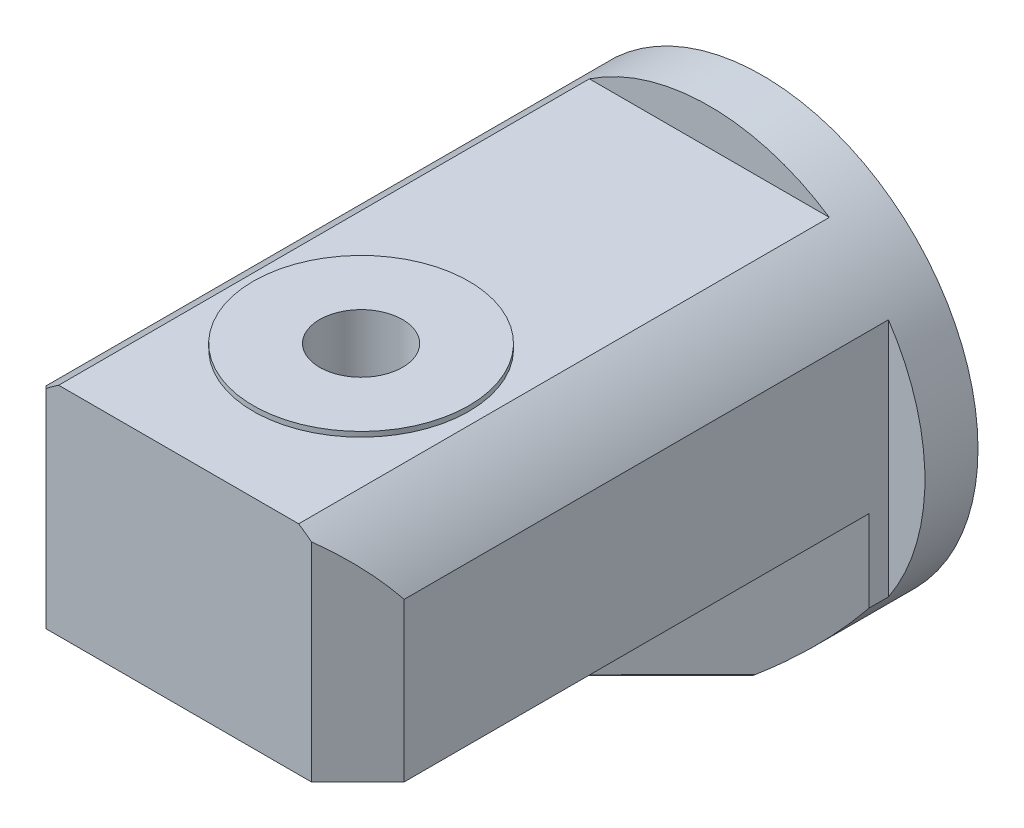
SolidWorks part; units mm, degrees
material "Cast Stainless Steel"
ref_plane "Front Plane" through (0, 0, 0) normal (0, 0, 1) x (1, 0, 0)
ref_plane "Top Plane" through (0, 0, 0) normal (0, 1, 0) x (1, 0, 0)
ref_plane "Right Plane" through (0, 0, 0) normal (1, 0, 0) x (0, 0, -1)
sketch "Sketch3" plane through (0, 0, 0) normal (0, 1, 0) x (1, 0, 0)
  circle A0 centre (0, 0) radius 130
extrude "Boss-Extrude1" add sketch "Sketch3" along normal blind 352
sketch "Sketch11" plane through (0, 352, 0) normal (0, 1, 0) x (1, 0, 0)
  line L0 (0, 0) -> (0, -108)
  line L1 (-72.3602, -108) -> (72.3602, -108)
  line L2 (0, 0) -> (-54.0967, 0)
  line L3 (-72.3602, 108) -> (72.3602, 108)
  line L4 (0, 0) -> (0, 40.1674)
  line L5 (0, 0) -> (108, 0)
  line L6 (108, 72.3602) -> (108, -72.3602)
  line L7 (-108, 72.3602) -> (-108, -72.3602)
  circle A0 centre (0, 0) radius 130 construction
  circle A2 centre (0, 0) radius 130
  circle A3 centre (0, 0) radius 130
  circle M1 centre (0, 0) radius 130
  dimension "D1" = 0
extrude "Cut-Extrude2" cut sketch "Sketch11" against normal blind 320 contours L1 M1 | L3 M1 region at (0, 352, 116.8671) region at (0, 352, -116.8671)
extrude "Cut-Extrude3" cut sketch "Sketch11<4>" against normal blind 320 contours L7 M1 | L6 M1 region at (116.8671, 352, 0) region at (-116.8671, 352, 0)
sketch "Sketch11<4>" plane through (0, 352, 0) normal (0, 1, 0) x (1, 0, 0) same geometry as "Sketch11"
sketch "Sketch12" plane through (-108, 0, 0) normal (-1, 0, 0) x (0, 0, 1)
  line L0 (0, 32) -> (0, 137)
  line L1 (-72.3602, 32) -> (72.3602, 32) construction
  line L2 (-72.3602, 137) -> (72.3602, 137)
  line L3 (-72.3602, 32) -> (-72.3602, 352) construction
  line L4 (72.3602, 32) -> (72.3602, 352) construction
  line L5 (72.3602, 32) -> (72.3602, 352)
  line L6 (-72.3602, 32) -> (-72.3602, 352)
  line L7 (-72.3602, 352) -> (72.3602, 352) construction
  line L8 (-72.3602, 352) -> (72.3602, 352)
  line L13 (72.3602, 352) -> (-72.3602, 352)
  line L14 (-72.3602, 352) -> (-72.3602, 32)
  line L15 (-72.3602, 32) -> (72.3602, 32)
  line L16 (72.3602, 32) -> (72.3602, 352)
  line L17 (72.3602, 352) -> (-72.3602, 352)
  line L18 (-72.3602, 352) -> (-72.3602, 32)
  line L19 (-72.3602, 32) -> (72.3602, 32)
  line L20 (72.3602, 32) -> (72.3602, 352)
  line M2 (72.3602, 352) -> (-72.3602, 352)
  line M3 (-72.3602, 352) -> (-72.3602, 32)
  line M5 (72.3602, 32) -> (72.3602, 352)
  dimension "D1" = 0
extrude "Cut-Extrude4" cut sketch "Sketch12" against normal blind 85 contours L2 M3 M5 M2 region at (-108, 244.5, 0)
sketch "Sketch14" plane through (-108, 0, 0) normal (-1, 0, 0) x (0, 0, 1)
  line L0 (-14.6151, 137) -> (14.6151, 137)
  line L1 (-72.3602, 137) -> (72.3602, 137) construction
  line L2 (14.6151, 137) -> (72.3602, 79.2549)
  line L3 (72.3602, 32) -> (72.3602, 137) construction
  line L4 (0, 137) -> (0, 116.7059)
  line L5 (-14.6151, 137) -> (-72.3602, 79.2549)
  line L10 (72.3602, 137) -> (-72.3602, 137)
  line L11 (-72.3602, 137) -> (-72.3602, 32)
  line L12 (-72.3602, 32) -> (72.3602, 32)
  line L13 (72.3602, 32) -> (72.3602, 137)
  line L14 (72.3602, 137) -> (-72.3602, 137)
  line L15 (-72.3602, 137) -> (-72.3602, 32)
  line L16 (-72.3602, 32) -> (72.3602, 32)
  line L17 (72.3602, 32) -> (72.3602, 137)
  line M8 (72.3602, 137) -> (-72.3602, 137)
  line M9 (-72.3602, 137) -> (-72.3602, 32)
  line M11 (72.3602, 32) -> (72.3602, 137)
  dimension "D1" = 0
extrude "Cut-Extrude5" cut sketch "Sketch14" against normal blind 85 contours L5 M8 M9 | L2 M8 M11 region at (-108, 117.7516, -53.1118) region at (-108, 117.7516, 53.1118)
sketch "Sketch15" plane through (0, 352, 0) normal (0, 1, 0) x (1, 0, 0)
  line L0 (-23, -72.3602) -> (-23, -108)
  line L1 (-72.3602, -108) -> (72.3602, -108) construction
  line L2 (-23, 72.3602) -> (-23, 108)
  line L3 (-72.3602, 108) -> (72.3602, 108) construction
  line L10 (-108, 72.3602) -> (-23, 72.3602)
  line L11 (-23, 72.3602) -> (-23, -72.3602)
  line L12 (-23, -72.3602) -> (-108, -72.3602)
  line L13 (-72.3602, -108) -> (72.3602, -108)
  line L14 (108, -72.3602) -> (108, 72.3602)
  line L15 (72.3602, 108) -> (-72.3602, 108)
  line L16 (-108, 72.3602) -> (-23, 72.3602)
  line L17 (-23, 72.3602) -> (-23, -72.3602)
  line L18 (-23, -72.3602) -> (-108, -72.3602)
  line L19 (-72.3602, -108) -> (72.3602, -108)
  line L20 (108, -72.3602) -> (108, 72.3602)
  line L21 (72.3602, 108) -> (-72.3602, 108)
  arc A4 (-108, -72.3602) -> (-72.3602, -108) centre (0, 0) ccw
  arc A5 (72.3602, -108) -> (108, -72.3602) centre (0, 0) ccw
  arc A6 (108, 72.3602) -> (72.3602, 108) centre (0, 0) ccw
  arc A7 (-72.3602, 108) -> (-108, 72.3602) centre (0, 0) ccw
  arc A8 (-108, -72.3602) -> (-72.3602, -108) centre (0, 0) ccw
  arc A9 (72.3602, -108) -> (108, -72.3602) centre (0, 0) ccw
  arc A10 (108, 72.3602) -> (72.3602, 108) centre (0, 0) ccw
  arc A11 (-72.3602, 108) -> (-108, 72.3602) centre (0, 0) ccw
  line M11 (-108, 72.3602) -> (-23, 72.3602)
  line M13 (-23, -72.3602) -> (-108, -72.3602)
  arc M14 (-108, -72.3602) -> (-72.3602, -108) centre (0, 0) ccw
  line M15 (-72.3602, -108) -> (72.3602, -108)
  line M19 (72.3602, 108) -> (-72.3602, 108)
  arc M20 (-72.3602, 108) -> (-108, 72.3602) centre (0, 0) ccw
  dimension "D1" = 0
extrude "Cut-Extrude7" cut sketch "Sketch15" against normal up to surface (308.3849 mm away) contours L2 M11 M19 M20 region at (-58.5006, 352, -88.6807) up to face at (-65.5, 108.1274, -43.4877)
extrude "Cut-Extrude8" cut sketch "Sketch15<4>" against normal up to surface (308.3849 mm away) contours L0 M13 M14 M15 region at (-58.5006, 352, 88.6807) up to face at (-65.5, 108.1274, 43.4877)
sketch "Sketch15<4>" plane through (0, 352, 0) normal (0, 1, 0) x (1, 0, 0) same geometry as "Sketch15"
sketch "Sketch18" plane through (-23, 0, 0) normal (-1, 0, 0) x (0, 0, 1)
  line L0 (-80, 352) -> (80, 352)
  line L1 (108, 352) -> (-108, 352) construction
  line L2 (80, 352) -> (108, 324)
  line L3 (108, 43.6151) -> (108, 352) construction
  line L4 (0, 352) -> (0, 328.1223)
  line L5 (-80, 352) -> (-108, 324)
  line L12 (108, 352) -> (-108, 352)
  line L13 (-108, 352) -> (-108, 43.6151)
  line L14 (-108, 43.6151) -> (-14.6151, 137)
  line L15 (-14.6151, 137) -> (14.6151, 137)
  line L16 (14.6151, 137) -> (108, 43.6151)
  line L17 (108, 43.6151) -> (108, 352)
  line L18 (108, 352) -> (-108, 352)
  line L19 (-108, 352) -> (-108, 43.6151)
  line L20 (-108, 43.6151) -> (-14.6151, 137)
  line L21 (-14.6151, 137) -> (14.6151, 137)
  line L22 (14.6151, 137) -> (108, 43.6151)
  line L23 (108, 43.6151) -> (108, 352)
  line M4 (108, 352) -> (-108, 352)
  line M5 (-108, 352) -> (-108, 43.6151)
  line M9 (108, 43.6151) -> (108, 352)
  dimension "D1" = 0
extrude "Cut-Extrude9" cut sketch "Sketch18" against normal blind 285 contours L5 M4 M5 | L2 M4 M9 region at (-23, 342.6667, -98.6667) region at (-23, 342.6667, 98.6667)
sketch "Sketch19" plane through (108, 0, 0) normal (1, 0, 0) x (0, 0, -1)
  line L0 (0, 352) -> (0, 242)
  line L1 (72.3602, 352) -> (-72.3602, 352) construction
  circle A0 centre (0, 242) radius 65
  dimension "D1" = 130
extrude "Boss-Extrude2" add sketch "Sketch19" along normal blind 3 contours A0 region at (108, 197.3381, 44.6619)
sketch "Sketch22" plane through (-108, 0, 0) normal (-1, 0, 0) x (0, 0, 1)
  line L0 (-14.6151, 137) -> (-72.3602, 79.2549) construction
  line L1 (-43.4877, 108.1274) -> (16.5123, 108.1274)
  line L2 (-43.4877, 108.1274) -> (-43.4877, 48.1274)
  line L3 (-43.4877, 48.1274) -> (16.5123, 48.1274)
  line L4 (16.5123, 108.1274) -> (16.5123, 48.1274)
  line L12 (14.6151, 137) -> (-14.6151, 137)
  line L13 (-14.6151, 137) -> (-72.3602, 79.2549)
  line L14 (-72.3602, 79.2549) -> (-72.3602, 32)
  line L15 (-72.3602, 32) -> (72.3602, 32)
  line L16 (72.3602, 32) -> (72.3602, 79.2549)
  line L17 (72.3602, 79.2549) -> (14.6151, 137)
  line L18 (14.6151, 137) -> (-14.6151, 137)
  line L19 (-14.6151, 137) -> (-72.3602, 79.2549)
  line L20 (-72.3602, 79.2549) -> (-72.3602, 32)
  line L21 (-72.3602, 32) -> (72.3602, 32)
  line L22 (72.3602, 32) -> (72.3602, 79.2549)
  line L23 (72.3602, 79.2549) -> (14.6151, 137)
  dimension "D1" = 0
extrude "Boss-Extrude3" add sketch "Sketch22" along normal blind 2 contours L4 L1 L2 L3 region at (-108, 78.1274, -13.4877)
fillet "Fillet1" radius 3 1 edges at (-109, 108.1274, -43.4877)
fillet "Fillet2" radius 3 3 edges at (-109, 48.1274, -43.4877) (-109, 48.1274, 16.5123) (-109, 108.1274, 16.5123)
fillet "Fillet4" radius 1 3 edges at (-108, 122.5637, -29.0514) (-108, 93.6912, -57.9239) (-108, 108.1274, 43.4877)
fillet "Fillet5" radius 1 8 edges at (-108, 107.2488, -42.609) (-108, 78.1274, -43.4877) (-108, 49.0061, -42.609) (-108, 48.1274, -13.4877) (-108, 49.0061, 15.6337) (-108, 78.1274, 16.5123) (-108, 107.2488, 15.6337) (-108, 108.1274, -13.4877)
move or copy body "Body-Move/Copy2" bodies to move or copy 113 copy no rotation origin (0, 0, 0) rotation axis (1, 0, 0) rotation angle 90
ref_plane "Plane1" through (0, 0, 362) normal (0, 0, 1) x (1, 0, 0)
sketch "Sketch29" plane through (0, 108, 0) normal (0, 1, 0) x (1, 0, 0)
  line L1 (56.7496, -229) -> (-6, -229)
  line L2 (56.7496, -229) -> (56.7496, -49)
  line L3 (56.7496, -49) -> (-6, -49)
  line L4 (-6, -229) -> (-6, -49)
  line L6 (-23, -324) -> (72.3602, -324)
  line L7 (-23, -324) -> (72.3602, -324)
  line L8 (72.3602, -324) -> (72.3602, -32)
  line L9 (72.3602, -324) -> (72.3602, -32)
  line L10 (72.3602, -32) -> (-72.3602, -32)
  line L11 (72.3602, -32) -> (-72.3602, -32)
  line L22 (-72.3602, -32) -> (-72.3602, -43.6151)
  line L23 (-72.3602, -32) -> (-72.3602, -43.6151)
  line L24 (-72.3602, -43.6151) -> (-23, -43.6151)
  line L25 (-72.3602, -43.6151) -> (-23, -43.6151)
  line L26 (-23, -43.6151) -> (-23, -324)
  line L27 (-23, -43.6151) -> (-23, -324)
  dimension "D5" = 180
  dimension "D1" = 0
sketch "Sketch31" plane through (-110, 0, 0) normal (-1, 0, 0) x (0, 0, 1)
  line L4 (105.1274, 43.4877) -> (51.1274, 43.4877)
  line L5 (48.1274, 40.4877) -> (48.1274, -13.5123)
  line L6 (51.1274, -16.5123) -> (105.1274, -16.5123)
  line L7 (108.1274, -13.5123) -> (108.1274, 40.4877)
  line L8 (105.1274, 43.4877) -> (51.1274, 43.4877)
  line L9 (48.1274, 40.4877) -> (48.1274, -13.5123)
  line L10 (51.1274, -16.5123) -> (105.1274, -16.5123)
  line L11 (108.1274, -13.5123) -> (108.1274, 40.4877)
  circle A0 centre (78.1274, 13.4877) radius 30
  circle A1 centre (78.1274, 13.4877) radius 20
  arc A4 (51.1274, 43.4877) -> (48.1274, 40.4877) centre (51.1274, 40.4877) ccw
  arc A5 (48.1274, -13.5123) -> (51.1274, -16.5123) centre (51.1274, -13.5123) ccw
  arc A6 (105.1274, -16.5123) -> (108.1274, -13.5123) centre (105.1274, -13.5123) ccw
  arc A7 (108.1274, 40.4877) -> (105.1274, 43.4877) centre (105.1274, 40.4877) ccw
  arc A8 (51.1274, 43.4877) -> (48.1274, 40.4877) centre (51.1274, 40.4877) ccw
  arc A9 (48.1274, -13.5123) -> (51.1274, -16.5123) centre (51.1274, -13.5123) ccw
  arc A10 (105.1274, -16.5123) -> (108.1274, -13.5123) centre (105.1274, -13.5123) ccw
  arc A11 (108.1274, 40.4877) -> (105.1274, 43.4877) centre (105.1274, 40.4877) ccw
  dimension "D1" = 0
  dimension "D2" = 10
move or copy body "Body-Move/Copy3" bodies to move or copy 116 copy no rotation origin (0, 0, 0) rotation axis (0, 0, -1) rotation angle 90
move or copy body "Body-Move/Copy4" bodies to move or copy 126 copy no rotation origin (0, 0, 0) rotation axis (0, 0, 1) rotation angle 180
sketch "Sketch35" plane through (0, -23, 0) normal (0, -1, 0) x (1, 0, 0)
  circle A0 centre (0, 242) radius 22.5
  circle A1 centre (0, 242) radius 65
  circle A4 centre (0, 242) radius 65
  dimension "D2" = 45
  dimension "D1" = 0
sketch "Sketch37" plane through (0, 111, 0) normal (0, 1, 0) x (1, 0, 0)
  circle A0 centre (0, -242) radius 25
  circle A1 centre (0, -242) radius 65
  circle A4 centre (0, -242) radius 65
  dimension "D2" = 50
  dimension "D1" = 0
extrude "Cut-Extrude20" cut sketch "Sketch37" against normal blind 50 contours A0 region at (0, 111, 242)
